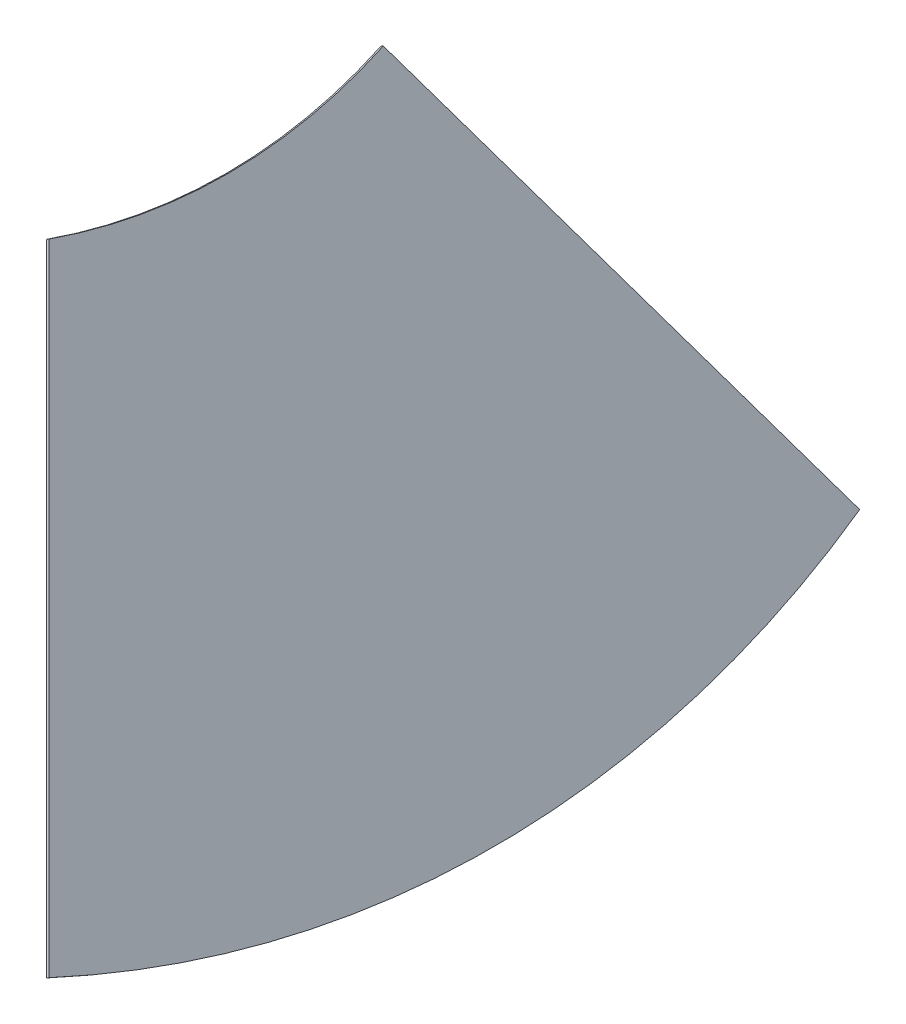
SolidWorks part; units mm, degrees
ref_plane "Front Plane" through (0, 0, 0) normal (0, 0, 1) x (1, 0, 0)
ref_plane "Top Plane" through (0, 0, 0) normal (0, 1, 0) x (1, 0, 0)
ref_plane "Right Plane" through (0, 0, 0) normal (1, 0, 0) x (0, 0, -1)
sketch "Sketch2" plane through (18.2002, 56.0419, 84.5047) normal (-0.86, -0.5103, 0) x (-0.3618, 0.6097, 0.7052)
  line L19 (-190.534, 33.1989) -> (-409.5071, -37.163)
  line L20 (-158.5303, -289.4784) -> (-87.0046, -70.8827)
  line L21 (-409.5071, -37.163) -> (-410.4784, -34.1402)
  line L25 (-410.4784, -34.1402) -> (-124.8613, 57.6361)
  line L26 (-65.2359, -4.3536) -> (-62.2184, -5.341)
  line L28 (-124.8613, 57.6361) -> (-123.89, 54.6133)
  line L29 (-124.8613, 57.6361) -> (-123.89, 54.6133)
  line L30 (-123.89, 54.6133) -> (-409.5071, -37.163)
  line L31 (-123.89, 54.6133) -> (-409.5071, -37.163) construction
  line L32 (-155.5128, -290.4658) -> (-158.5303, -289.4784)
  line L34 (-158.5303, -289.4784) -> (-65.2359, -4.3536)
  line L35 (-158.5303, -289.4784) -> (-65.2359, -4.3536) construction
  line L36 (-65.2359, -4.3536) -> (-62.2184, -5.341)
  line L37 (-65.2359, -4.3536) -> (-62.2184, -5.341)
  line L38 (-62.2184, -5.341) -> (-155.5128, -290.4658)
  line L39 (-65.2359, -4.3536) -> (-158.5303, -289.4784) construction
  arc A0 (-158.5303, -289.4784) -> (-409.5071, -37.163) centre (24.7046, 143.7646) cw
  arc A2 (-190.534, 33.1989) -> (-87.0046, -70.8827) centre (39.0787, 158.0625) ccw
  dimension "D1" = 230
extrude "Boss-Extrude1" add sketch "Sketch2" along normal mid plane 1.27 contours L19 A2 L20 A0 | A2 L20 A0 L19 region at (143.1227, -154.5019, 0)
